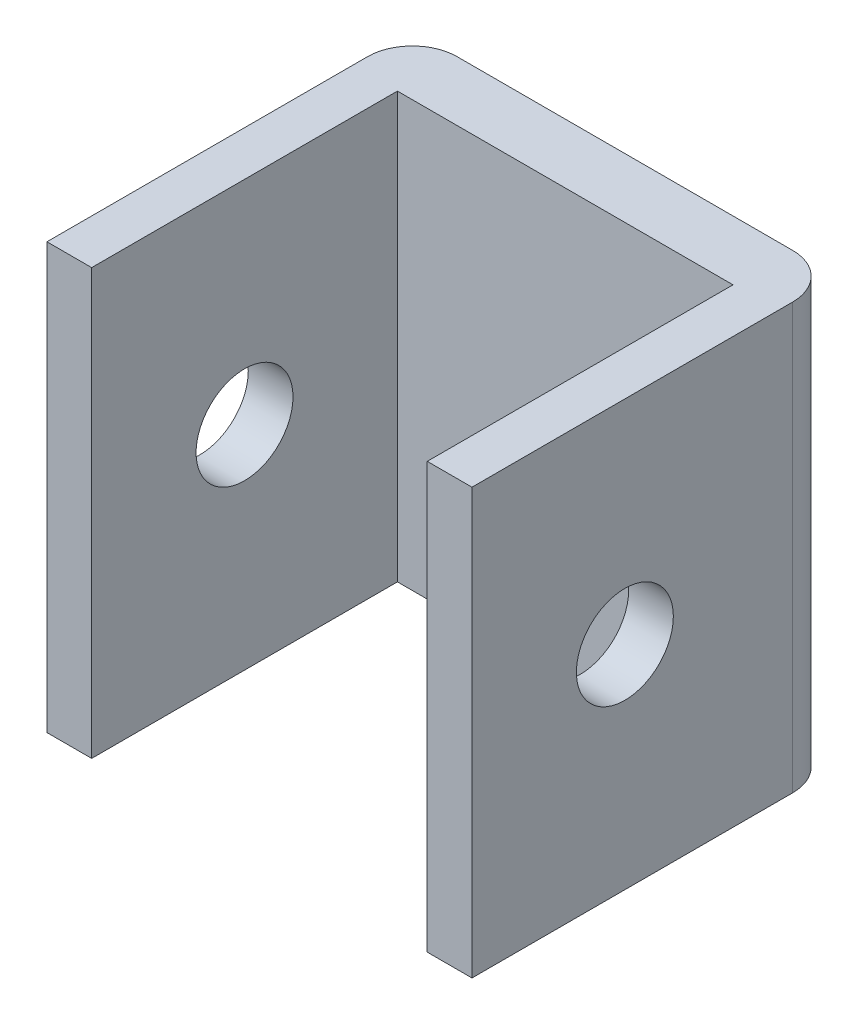
SolidWorks part; units mm, degrees
ref_plane "Front Plane" through (0, 0, 0) normal (0, 0, 1) x (1, 0, 0)
ref_plane "Top Plane" through (0, 0, 0) normal (0, 1, 0) x (1, 0, 0)
ref_plane "Right Plane" through (0, 0, 0) normal (1, 0, 0) x (0, 0, -1)
sketch "Sketch1" plane through (0, 0, 0) normal (0, 1, 0) x (1, 0, 0)
  line L1 (-14.25, -12.25) -> (14.25, -12.25)
  line L2 (-14.25, -12.25) -> (-14.25, 9.25)
  line L3 (-11.25, 12.25) -> (11.25, 12.25)
  line L4 (14.25, -12.25) -> (14.25, 9.25)
  line L5 (-14.25, -12.25) -> (14.25, 12.25) construction
  line L6 (-14.25, 12.25) -> (14.25, -12.25) construction
  line L7 (-11.25, 8.25) -> (11.25, 8.25)
  line L8 (-11.25, 8.25) -> (-11.25, -12.25)
  line L9 (-11.25, -12.25) -> (11.25, -12.25)
  line L10 (11.25, 8.25) -> (11.25, -12.25)
  arc A0 (11.25, 12.25) -> (14.25, 9.25) centre (11.25, 9.25) cw
  arc A1 (-14.25, 9.25) -> (-11.25, 12.25) centre (-11.25, 9.25) cw
  point P0 (0, 0)
  point P10 (0, 0)
  dimension "D6" = 3
  dimension "D1" = 24.5
  dimension "D2" = 28.5
  dimension "D3" = 3
  dimension "D4" = 3
  dimension "D5" = 20.5
extrude "Boss-Extrude1" add sketch "Sketch1" along normal blind 14.25 and the other way blind 14.25 contours A1 L2 L1 L8 L7 L10 L4 A0 L3 region at (-13.8742, 0, 1.5)
sketch "Sketch2" plane through (0, 0, -12.25) normal (0, 0, -1) x (-1, 0, 0)
  circle A0 centre (0, 0) radius 5
extrude "Boss-Extrude2" add sketch "Sketch2" along normal blind 7
sketch "Sketch3" plane through (0, 0, -19.25) normal (0, 0, -1) x (-1, 0, 0)
  circle A0 centre (0, 0) radius 2.25
extrude "Cut-Extrude1" cut sketch "Sketch3" against normal blind 1.5
sketch "Sketch4" plane through (0, 0, -17.75) normal (0, 0, -1) x (-1, 0, 0)
  circle A0 centre (0, 0) radius 1.5
extrude "Cut-Extrude2" cut sketch "Sketch4" against normal blind 10.5
sketch "Sketch5" plane through (14.25, 0, 0) normal (1, 0, 0) x (0, 0, -1)
  line L0 (-12.25, -14.25) -> (-12.25, 14.25) construction
  circle A0 centre (-2, 0) radius 3.25
  point P2 (0, 0)
  dimension "D1" = 10.25
extrude "Cut-Extrude3" cut sketch "Sketch5" against normal blind 32.5
